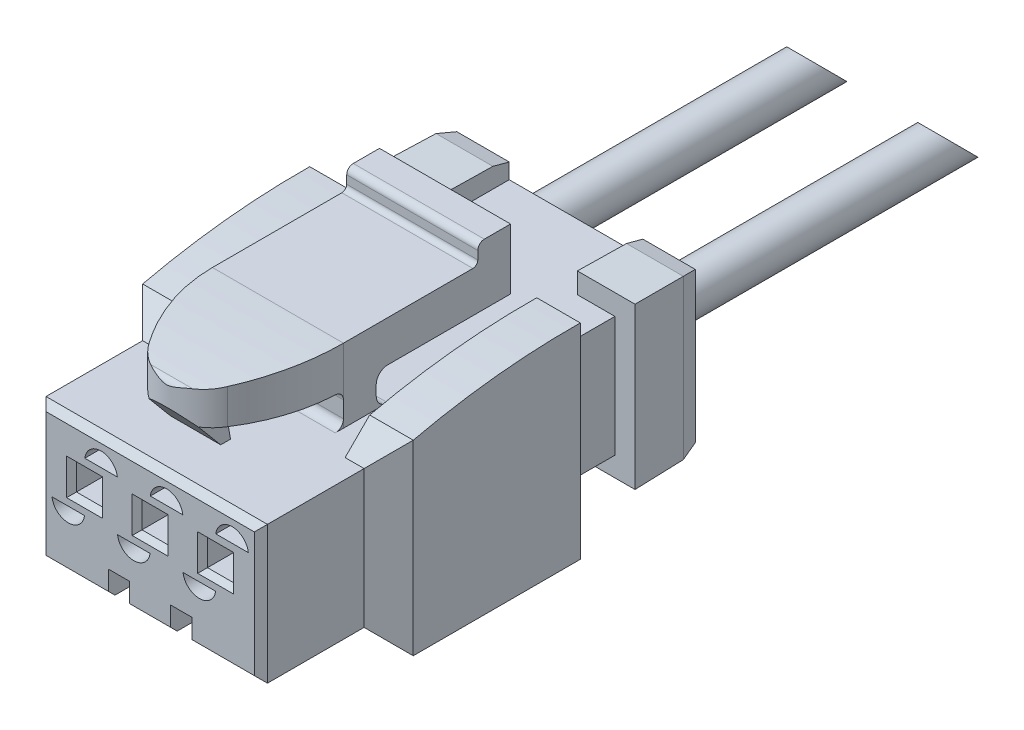
SolidWorks part; units mm, degrees
ref_plane "Front Plane" through (0, 0, 0) normal (0, 0, 1) x (1, 0, 0)
ref_plane "Top Plane" through (0, 0, 0) normal (0, 1, 0) x (1, 0, 0)
ref_plane "Right Plane" through (0, 0, 0) normal (1, 0, 0) x (0, 0, -1)
sketch "Sketch1" plane through (0, 0, 0) normal (1, 0, 0) x (0, 0, -1)
  line L0 (-13, 1.4) -> (-13, -2.4)
  line L1 (-13, -2.4) -> (-12.8, -2.6)
  line L2 (-12.8, -2.6) -> (-9.85, -2.6)
  line L3 (-9.85, -2.6) -> (-9.1, -3.35)
  line L4 (-9.1, -3.35) -> (-4, -3.35)
  line L5 (-4, -3.35) -> (-4, -2.07)
  line L6 (-4, -2.07) -> (-2, -2.07)
  line L7 (-2, -2.07) -> (-2, -2.67)
  line L8 (-2, -2.67) -> (-0.5, -2.6438)
  line L9 (-0.5, -2.6438) -> (0, -2.5098)
  line L10 (0, -2.5098) -> (0, 2.0698)
  line L11 (0, 2.0698) -> (-0.5, 2.2038)
  line L12 (-0.5, 2.2038) -> (-2, 2.23)
  line L13 (-2, 2.23) -> (-2, 1.6)
  line L14 (-2, 1.6) -> (-4, 1.6)
  line L15 (-4, 1.6) -> (-4, 2.9)
  line L16 (-9.1, 2.35) -> (-9.85, 1.6)
  line L17 (-9.85, 1.6) -> (-12.8, 1.6)
  line L18 (-12.8, 1.6) -> (-13, 1.4)
  arc A0 (-4, 2.9) -> (-9.1, 2.35) centre (-4.2515, -18.6885) ccw
extrude "Boss-Extrude1" add sketch "Sketch1" against normal blind 4.15 and the other way blind 4.15
sketch "Sketch2" plane through (0, 0, 0) normal (0, 1, 0) x (1, 0, 0)
  line L0 (-5, -14) -> (5, -14)
  line L1 (5, -14) -> (5, 1)
  line L2 (5, 1) -> (-5, 1)
  line L3 (-5, 1) -> (-5, -14)
  line L4 (-4.13, -9.1) -> (-3.38, -9.85)
  line L5 (-3.38, -9.85) -> (-3.38, -12.8)
  line L6 (-3.38, -12.8) -> (-3.18, -13)
  line L7 (-3.18, -13) -> (3.18, -13)
  line L8 (3.18, -13) -> (3.38, -12.8)
  line L9 (3.38, -12.8) -> (3.38, -9.85)
  line L10 (3.38, -9.85) -> (4.13, -9.1)
  line L11 (4.13, -9.1) -> (4.13, -4)
  line L12 (4.13, -4) -> (3.185, -4)
  line L13 (3.185, -4) -> (3.185, -2)
  line L14 (3.185, -2) -> (3.8, -2)
  line L15 (3.8, -2) -> (3.7738, -0.5)
  line L16 (3.7738, -0.5) -> (3.6398, 0)
  line L17 (3.6398, 0) -> (-3.6398, 0)
  line L18 (-3.6398, 0) -> (-3.7738, -0.5)
  line L19 (-3.7738, -0.5) -> (-3.8, -2)
  line L20 (-3.8, -2) -> (-3.185, -2)
  line L21 (-3.185, -2) -> (-3.185, -4)
  line L22 (-3.185, -4) -> (-4.13, -4)
  line L23 (-4.13, -4) -> (-4.13, -9.1)
extrude "Cut-Extrude1" cut sketch "Sketch2" along normal blind 6 and the other way blind 6
ref_plane "Plane1" through (0, 1.6, 0) normal (0, 1, 0) x (1, 0, 0)
sketch "Sketch3" plane through (0, 1.6, 0) normal (0, 1, 0) x (1, 0, 0)
  line L0 (-2.8, -4) -> (-2.8, -13)
  line L1 (-2.8, -13) -> (2.8, -13)
  line L2 (2.8, -13) -> (2.8, -4)
  line L3 (2.8, -4) -> (2.04, -4)
  line L4 (2.04, -4) -> (2.04, 0)
  line L5 (2.04, 0) -> (-2.04, 0)
  line L6 (-2.04, 0) -> (-2.04, -4)
  line L7 (-2.04, -4) -> (-2.8, -4)
extrude "Cut-Extrude2" cut sketch "Sketch3" along normal blind 2
sketch "Sketch4" plane through (0, 0, 0) normal (1, 0, 0) x (0, 0, -1)
  line L0 (-12.51, 3.3881) -> (-12.51, 2.87)
  line L1 (-12.51, 2.87) -> (-11.6122, 1.8)
  line L2 (-11.6122, 1.8) -> (-11.3122, 1.8)
  line L3 (-11.3122, 1.8) -> (-11.4118, 2.3653)
  line L4 (-11.2149, 2.6) -> (-9.35, 2.6)
  line L5 (-9.1, 2.35) -> (-9.1, 1.85)
  line L6 (-9.35, 1.6) -> (-9.35, 0.6)
  line L7 (-9.35, 0.6) -> (-7.75, 0.6)
  line L8 (-7.75, 0.6) -> (-7.75, 1.6)
  line L9 (-8.1, 1.95) -> (-8.1, 2.25)
  line L10 (-7.75, 2.6) -> (-4, 2.6)
  line L11 (-4, 2.6) -> (-4, 4.45)
  line L12 (-4, 4.45) -> (-4.8, 4.45)
  line L13 (-5, 4.25) -> (-5, 4)
  line L14 (-5.15, 3.85) -> (-9.1, 3.85)
  arc A0 (-11.4118, 2.3653) -> (-11.2149, 2.6) centre (-11.2149, 2.4) cw
  arc A1 (-9.35, 2.6) -> (-9.1, 2.35) centre (-9.35, 2.35) cw
  arc A2 (-9.1, 1.85) -> (-9.35, 1.6) centre (-9.35, 1.85) cw
  arc A3 (-7.75, 1.6) -> (-8.1, 1.95) centre (-7.75, 1.95) cw
  arc A4 (-8.1, 2.25) -> (-7.75, 2.6) centre (-7.75, 2.25) cw
  arc A5 (-4.8, 4.45) -> (-5, 4.25) centre (-4.8, 4.25) ccw
  arc A6 (-5, 4) -> (-5.15, 3.85) centre (-5.15, 4) cw
  arc A7 (-9.1, 3.85) -> (-12.3424, 3.5854) centre (-9.1, -16.15) ccw
  arc A8 (-12.3424, 3.5854) -> (-12.51, 3.3881) centre (-12.31, 3.3881) ccw
extrude "Boss-Extrude2" add sketch "Sketch4" against normal blind 2 and the other way blind 2
sketch "Sketch5" plane through (0, 1.6, 0) normal (0, 1, 0) x (1, 0, 0)
  line L0 (-2.2, -12.8) -> (2.2, -12.8)
  line L1 (2.2, -12.8) -> (2.2, -3.8)
  line L2 (2.2, -3.8) -> (-2.2, -3.8)
  line L3 (-2.2, -3.8) -> (-2.2, -12.8)
  line L4 (2, -9.1) -> (2, -4)
  line L5 (2, -4) -> (-2, -4)
  line L6 (-2, -4) -> (-2, -9.1)
  arc A0 (-2, -9.1) -> (-1.1898, -11.8286) centre (3, -9.1) ccw
  arc A1 (-1.1898, -11.8286) -> (1.1898, -11.8286) centre (0, -11.11) ccw
  arc A2 (1.1898, -11.8286) -> (2, -9.1) centre (-3, -9.1) ccw
extrude "Cut-Extrude3" cut sketch "Sketch5" along normal blind 3
sketch "Sketch6" plane through (0, 1.6, 0) normal (0, 1, 0) x (1, 0, 0)
  line L0 (-2, -10.5) -> (-2, -13)
  line L1 (-2, -13) -> (-0.765, -13)
  line L2 (-0.765, -13) -> (-0.765, -10.7)
  line L3 (-0.765, -10.7) -> (0.765, -10.7)
  line L4 (0.765, -10.7) -> (0.765, -13)
  line L5 (0.765, -13) -> (2, -13)
  line L6 (2, -13) -> (2, -10.5)
  line L7 (2, -10.5) -> (0.765, -10.5)
  line L8 (0.765, -10.5) -> (0.765, -4)
  line L9 (0.765, -4) -> (2, -4)
  line L10 (2, -4) -> (2, -3)
  line L11 (2, -3) -> (-2, -3)
  line L12 (-2, -3) -> (-2, -4)
  line L13 (-2, -4) -> (-0.765, -4)
  line L14 (-0.765, -4) -> (-0.765, -10.5)
  line L15 (-0.765, -10.5) -> (-2, -10.5)
extrude "Cut-Extrude4" cut sketch "Sketch6" along normal blind 1
ref_plane "Plane2" through (0, 0, 4) normal (0, 0, 1) x (1, 0, 0)
sketch "Sketch7" plane through (0, 0, 4) normal (0, 0, 1) x (1, 0, 0)
  line L0 (-2.3, -3.35) -> (-2.1906, -3.35)
  line L1 (2.1906, -3.35) -> (2.3, -3.35)
  line L2 (2.3, -3.35) -> (2, 0)
  line L3 (2, 0) -> (-2, 0)
  line L4 (-2, 0) -> (-2.3, -3.35)
  arc A0 (-2.1906, -3.35) -> (-1.9953, -3.5068) centre (-2.1906, -3.55) cw
  arc A1 (-1.9953, -3.5068) -> (-1.8621, -3.6537) centre (-1.8, -3.4636) ccw
  arc A2 (-1.8621, -3.6537) -> (1.8621, -3.6537) centre (0, 2.05) ccw
  arc A3 (1.8621, -3.6537) -> (1.9953, -3.5068) centre (1.8, -3.4636) ccw
  arc A4 (1.9953, -3.5068) -> (2.1906, -3.35) centre (2.1906, -3.55) cw
extrude "Boss-Extrude3" add sketch "Sketch7" along normal blind 1
ref_plane "Plane3" through (0, 0, 9.85) normal (0, 0, 1) x (1, 0, 0)
sketch "Sketch8" plane through (0, 0, 9.85) normal (0, 0, 1) x (1, 0, 0)
  line L0 (-1.275, -1.81) -> (-1.275, -3.41)
  line L1 (-1.275, -3.41) -> (1.275, -3.41)
  line L2 (1.275, -3.41) -> (1.275, -1.81)
  line L3 (1.275, -1.81) -> (0.625, -1.81)
  line L4 (0.625, -1.81) -> (0.625, -2.61)
  line L5 (0.625, -2.61) -> (-0.625, -2.61)
  line L6 (-0.625, -2.61) -> (-0.625, -1.81)
  line L7 (-0.625, -1.81) -> (-1.275, -1.81)
extrude "Cut-Extrude5" cut sketch "Sketch8" along normal blind 3.2
ref_plane "Plane4" through (0, 0, 13) normal (0, 0, 1) x (1, 0, 0)
sketch "Sketch9" plane through (0, 0, 13) normal (0, 0, 1) x (1, 0, 0)
  line L0 (-2.4, 0.39) -> (-2.4, -0.41)
  line L1 (-2.4, -0.41) -> (-1.6, -0.41)
  line L2 (-1.6, -0.41) -> (-1.6, 0.39)
  line L3 (-1.6, 0.39) -> (-2.4, 0.39)
extrude "Cut-Extrude6" cut sketch "Sketch9" against normal blind 2.9
sketch "Sketch10" plane through (0, 0, 13) normal (0, 0, 1) x (1, 0, 0)
  line L0 (-0.4, 0.39) -> (-0.4, -0.41)
  line L1 (-0.4, -0.41) -> (0.4, -0.41)
  line L2 (0.4, -0.41) -> (0.4, 0.39)
  line L3 (0.4, 0.39) -> (-0.4, 0.39)
extrude "Cut-Extrude7" cut sketch "Sketch10" against normal blind 2.9
sketch "Sketch11" plane through (0, 0, 13) normal (0, 0, 1) x (1, 0, 0)
  line L0 (1.6, 0.39) -> (1.6, -0.41)
  line L1 (1.6, -0.41) -> (2.4, -0.41)
  line L2 (2.4, -0.41) -> (2.4, 0.39)
  line L3 (2.4, 0.39) -> (1.6, 0.39)
extrude "Cut-Extrude8" cut sketch "Sketch11" against normal blind 2.9
sketch "Sketch12" plane through (0, 0, 13) normal (0, 0, 1) x (1, 0, 0)
  line L0 (-2.0036, -0.76) -> (-2.9964, -0.76)
  arc A0 (-2.9964, -0.76) -> (-2.0036, -0.76) centre (-2.5, -0.7) ccw
extrude "Cut-Extrude9" cut sketch "Sketch12" against normal blind 2.9
sketch "Sketch13" plane through (0, 0, 13) normal (0, 0, 1) x (1, 0, 0)
  line L0 (0.0036, 0.76) -> (0.9964, 0.76)
  arc A0 (0.9964, 0.76) -> (0.0036, 0.76) centre (0.5, 0.7) ccw
extrude "Cut-Extrude10" cut sketch "Sketch13" against normal blind 2.9
sketch "Sketch14" plane through (0, 0, 13) normal (0, 0, 1) x (1, 0, 0)
  line L0 (2.0036, 0.76) -> (2.9964, 0.76)
  arc A0 (2.9964, 0.76) -> (2.0036, 0.76) centre (2.5, 0.7) ccw
extrude "Cut-Extrude11" cut sketch "Sketch14" against normal blind 2.9
sketch "Sketch15" plane through (0, 0, 13) normal (0, 0, 1) x (1, 0, 0)
  line L0 (-1.9964, 0.76) -> (-1.0036, 0.76)
  arc A0 (-1.0036, 0.76) -> (-1.9964, 0.76) centre (-1.5, 0.7) ccw
extrude "Cut-Extrude12" cut sketch "Sketch15" against normal blind 2.9
sketch "Sketch16" plane through (0, 0, 13) normal (0, 0, 1) x (1, 0, 0)
  line L0 (-0.0036, -0.76) -> (-0.9964, -0.76)
  arc A0 (-0.9964, -0.76) -> (-0.0036, -0.76) centre (-0.5, -0.7) ccw
extrude "Cut-Extrude13" cut sketch "Sketch16" against normal blind 2.9
sketch "Sketch17" plane through (0, 0, 13) normal (0, 0, 1) x (1, 0, 0)
  line L0 (1.9964, -0.76) -> (1.0036, -0.76)
  arc A0 (1.0036, -0.76) -> (1.9964, -0.76) centre (1.5, -0.7) ccw
extrude "Cut-Extrude14" cut sketch "Sketch17" against normal blind 2.9
ref_plane "Plane5" through (0, -0.56, 0) normal (0, 1, 0) x (1, 0, 0)
sketch "Sketch18" plane through (0, -0.56, 0) normal (0, 1, 0) x (1, 0, 0)
  line L0 (-2.55, -13) -> (-2.55, -13.5)
  line L1 (-2.55, -13.5) -> (2.55, -13.5)
  line L2 (2.55, -13.5) -> (2.55, -13)
  line L3 (2.55, -13) -> (2.05, -12.5)
  line L4 (2.05, -12.5) -> (1.95, -12.5)
  line L5 (1.95, -12.5) -> (1.45, -13)
  line L6 (1.45, -13) -> (0.55, -13)
  line L7 (0.55, -13) -> (0.05, -12.5)
  line L8 (0.05, -12.5) -> (-0.05, -12.5)
  line L9 (-0.05, -12.5) -> (-0.55, -13)
  line L10 (-0.55, -13) -> (-1.45, -13)
  line L11 (-1.45, -13) -> (-1.95, -12.5)
  line L12 (-1.95, -12.5) -> (-2.05, -12.5)
  line L13 (-2.05, -12.5) -> (-2.55, -13)
extrude "Cut-Extrude15" cut sketch "Sketch18" along normal blind 1.1
sketch "Sketch19" plane through (0, 0, 0) normal (1, 0, 0) x (0, 0, -1)
  line L0 (-13, 0.54) -> (-12.85, 0.39)
  line L1 (-12.85, 0.39) -> (-8.1, 0.39)
  line L2 (-8.1, 0.39) -> (-8.1, -0.41)
  line L3 (-8.1, -0.41) -> (-12.85, -0.41)
  line L4 (-12.85, -0.41) -> (-13, -0.56)
  line L5 (-13, -0.56) -> (-8, -0.56)
  line L6 (-8, -0.56) -> (-8, 0.54)
  line L7 (-8, 0.54) -> (-13, 0.54)
extrude "Boss-Extrude4" add sketch "Sketch19" against normal blind 3 and the other way blind 3
sketch "Sketch20" plane through (0, 0, 0) normal (0, 0, 1) x (1, 0, 0)
  circle A0 centre (2, 0) radius 0.65
extrude "Boss-Extrude5" add sketch "Sketch20" against normal blind 10
sketch "Sketch21" plane through (0, 0, 0) normal (0, 0, 1) x (1, 0, 0)
  circle A0 centre (-2, 0) radius 0.65
extrude "Boss-Extrude6" add sketch "Sketch21" against normal blind 10
sketch "Sketch22" plane through (0, 0, 0) normal (1, 0, 0) x (0, 0, -1)
  line L0 (8.5, 0.85) -> (10, -0.65)
  line L1 (10, -0.65) -> (10, 0.85)
  line L2 (10, 0.85) -> (8.5, 0.85)
extrude "Cut-Extrude16" cut sketch "Sketch22" along normal blind 3 and the other way blind 3
ref_plane "Plane6" through (0, -0.2, 0) normal (0, 1, 0) x (1, 0, 0)
ref_plane "Plane7" through (0, 0, -50) normal (0, 0, 1) x (1, 0, 0)
ref_plane "ANBAU XY" through (0, 0, 13) normal (0, 0, -1) x (-1, 0, 0)
ref_plane "ANBAU XZ" through (0, 0, 0) normal (0, 1, 0) x (1, 0, 0)
ref_plane "ANBAU YZ" through (0, 0, 0) normal (1, 0, 0) x (0, 0, -1)
ref_axis "ANBAU X" through (-80.9, 0, 13) along (1, 0, 0)
ref_axis "ANBAU Y" through (0, 50, 13) along (0, -1, 0)
ref_axis "ANBAU Z" through (0, 0, -80.9) along (0, 0, 1)
sketch3d "ANBAU"
  point P0 (0, 0, 13)
ref_plane "NEBV XY" through (0, 0, 13) normal (0, 0, 1) x (1, 0, 0)
ref_plane "NEBV XZ" through (0, 0.1, 0) normal (0, -1, 0) x (-1, 0, 0)
ref_plane "NEBV YZ" through (0, 0, 0) normal (1, 0, 0) x (0, 0, -1)
ref_axis "NEBV X" through (-80.9, 0.1, 13) along (1, 0, 0)
ref_axis "NEBV Y" through (0, -50, 13) along (0, 1, 0)
ref_axis "NEBV Z" through (0, 0.1, 80.9) along (0, 0, -1)
sketch3d "NEBV"
  point P0 (0, 0.1, 13)
sketch "Sketch23" plane through (0, 0, 10.1) normal (0, 0, 1) x (1, 0, 0)
  line L0 (2.4, 0.39) -> (1.6, 0.39) construction
  line L1 (1.6, 0.39) -> (1.6, -0.41) construction
  line L2 (1.6, -0.41) -> (2.4, -0.41) construction
  line L3 (2.4, -0.41) -> (2.4, 0.39) construction
  line L4 (0.4, 0.39) -> (-0.4, 0.39) construction
  line L5 (-0.4, 0.39) -> (-0.4, -0.41) construction
  line L6 (-0.4, -0.41) -> (0.4, -0.41) construction
  line L7 (0.4, -0.41) -> (0.4, 0.39) construction
  line L8 (-1.6, 0.39) -> (-2.4, 0.39) construction
  line L9 (-2.4, 0.39) -> (-2.4, -0.41) construction
  line L10 (-2.4, -0.41) -> (-1.6, -0.41) construction
  line L11 (-1.6, -0.41) -> (-1.6, 0.39) construction
  line L12 (2.4, 0.39) -> (1.6, 0.39)
  line L13 (1.6, 0.39) -> (1.6, -0.41)
  line L14 (1.6, -0.41) -> (2.4, -0.41)
  line L15 (2.4, -0.41) -> (2.4, 0.39)
  line L16 (0.4, 0.39) -> (-0.4, 0.39)
  line L17 (-0.4, 0.39) -> (-0.4, -0.41)
  line L18 (-0.4, -0.41) -> (0.4, -0.41)
  line L19 (0.4, -0.41) -> (0.4, 0.39)
  line L20 (-1.6, 0.39) -> (-2.4, 0.39)
  line L21 (-2.4, 0.39) -> (-2.4, -0.41)
  line L22 (-2.4, -0.41) -> (-1.6, -0.41)
  line L23 (-1.6, -0.41) -> (-1.6, 0.39)
  point P0 (2, -0.01)
  point P1 (0, -0.01)
  point P2 (-2, -0.01)
  point P4 (0, 0)
  point P7 (0, 0)
  point P9 (0, 0)
  point P11 (0, -0.0588)
  point P12 (2, 0.39)
  point P15 (0, 0)
  point P17 (0, 0.39)
  point P19 (0, 0)
  point P20 (0, 0)
  point P23 (-2, 0.39)
  point P25 (0, 0)
  point P27 (-2.4, -0.01)
other "CPoint1" parameters "Diameter"=25.4, "StubLength"=38.1
ref_axis "Axis1" through (2, -0.01, 20.1) along (0, 0, -1)
other "CPoint2" parameters "Diameter"=25.4, "StubLength"=38.1
ref_axis "Axis2" through (0, -0.01, 20.1) along (0, 0, -1)
other "CPoint3" parameters "Diameter"=25.4, "StubLength"=38.1
ref_axis "Axis3" through (-2, -0.01, 20.1) along (0, 0, -1)
